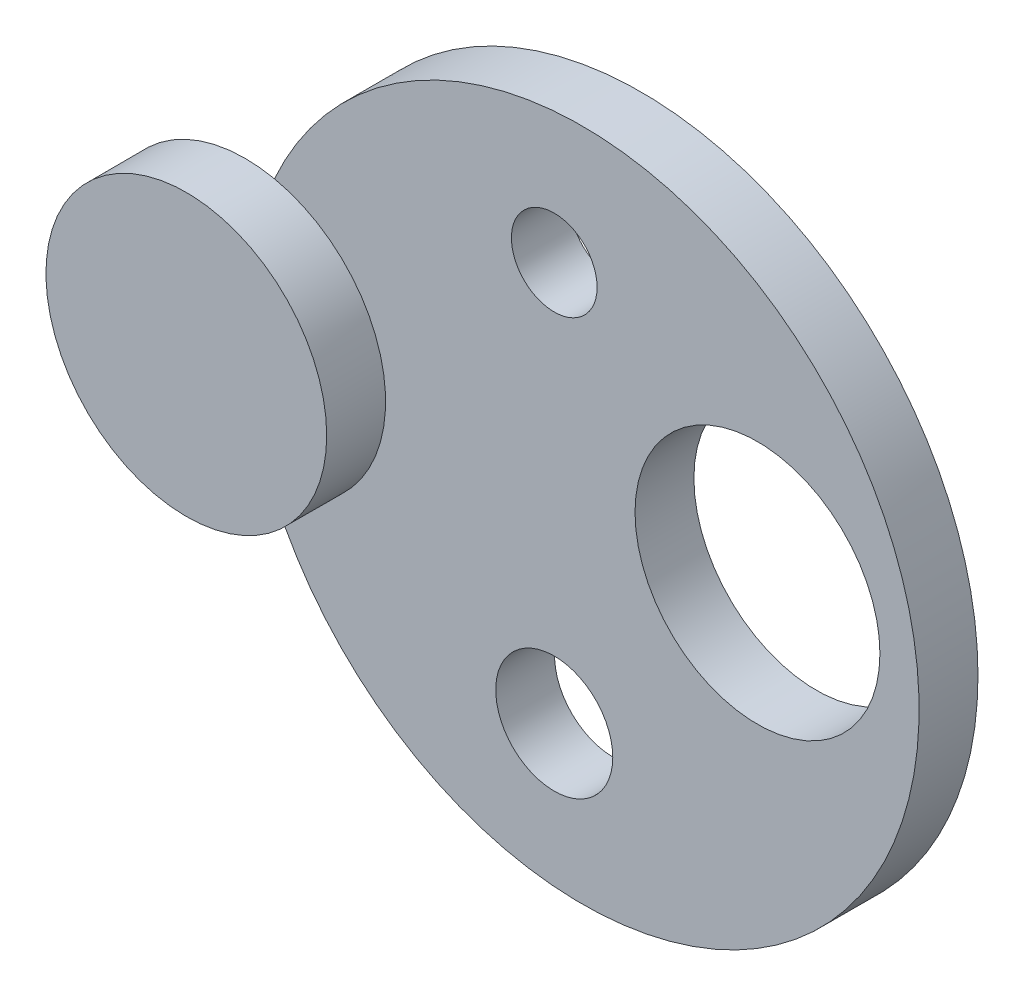
SolidWorks part; units mm, degrees
ref_plane "Alzado" through (0, 0, 0) normal (0, 0, 1) x (1, 0, 0)
ref_plane "Planta" through (0, 0, 0) normal (0, 1, 0) x (1, 0, 0)
ref_plane "Vista lateral" through (0, 0, 0) normal (1, 0, 0) x (0, 0, -1)
sketch "Croquis1" plane through (0, 0, 0) normal (0, 0, 1) x (1, 0, 0)
  circle A0 centre (0, 0) radius 57.2267
  circle A1 centre (-4.742, 34.7594) radius 7.278
  circle A2 centre (-4.742, -33.0459) radius 9.9402
  circle A3 centre (29.7726, 4.8957) radius 20.7966
extrude "Saliente-Extruir1" add sketch "Croquis1" along normal blind 10
sketch "Croquis2" plane through (0, 0, 10) normal (0, 0, 1) x (1, 0, 0)
  circle A0 centre (-57.2267, 0) radius 23.8429
  circle A1 centre (0, 0) radius 57.2267 construction
extrude "Saliente-Extruir2" add sketch "Croquis2" along normal blind 10
